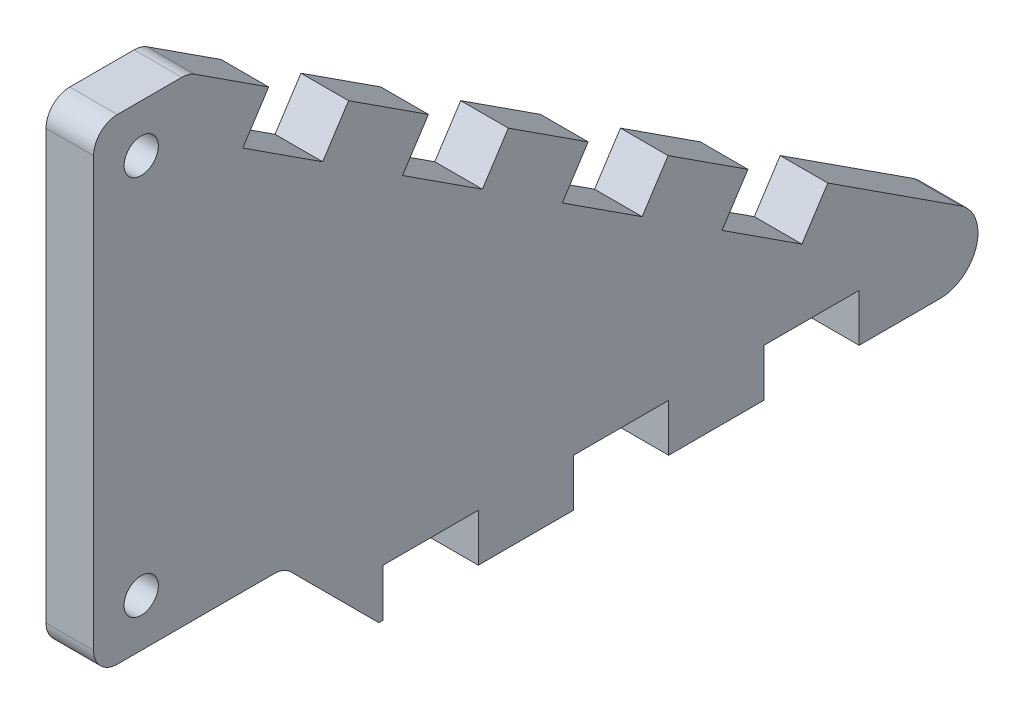
SolidWorks part; units mm, degrees
material "Custom Plastic"
ref_plane "Front Plane" through (0, 0, 0) normal (0, 0, 1) x (1, 0, 0)
ref_plane "Top Plane" through (0, 0, 0) normal (0, 1, 0) x (1, 0, 0)
ref_plane "Right Plane" through (0, 0, 0) normal (1, 0, 0) x (0, 0, -1)
sketch "Sketch2" plane through (0, 0, 0) normal (1, 0, 0) x (0, 0, -1)
  line L0 (0, 0) -> (0, 26.924) construction
  line L1 (0, 26.924) -> (0, 77.724) construction
  line L2 (-65.278, 77.724) -> (0, 77.724) construction
  line L3 (-71.628, 77.724) -> (-71.628, 26.924) construction
  line L4 (-71.628, 26.924) -> (0, 26.924) construction
  line L5 (-45.72, 0) -> (45.72, 0)
  line L6 (-77.978, 84.074) -> (-77.978, 20.574)
  line L7 (45.72, 7.9375) -> (-45.72, 7.9375)
  line L8 (45.72, 0) -> (52.07, 0)
  line L9 (-77.978, 20.574) -> (-45.72, 0)
  line L10 (-65.278, 84.074) -> (52.07, 7.9375)
  line L11 (-71.628, 77.724) -> (-71.628, 84.074) construction
  line L12 (-71.628, 77.724) -> (-77.978, 77.724) construction
  line L13 (-71.628, 26.924) -> (-77.978, 26.924) construction
  line L14 (-71.628, 26.924) -> (-71.628, 20.574) construction
  line L15 (-65.278, 84.074) -> (-77.978, 84.074)
  line L16 (-71.628, 77.724) -> (-65.278, 77.724) construction
  line L17 (-52.578, 20.574) -> (-39.9415, 7.9375)
  line L18 (-65.278, 77.724) -> (-65.278, 84.074) construction
  line L19 (-77.978, 20.574) -> (-52.578, 20.574)
  line L21 (52.07, 0) -> (52.07, 7.9375)
  line L22 (52.07, 7.9375) -> (45.72, 7.9375)
  circle A0 centre (-71.628, 77.724) radius 2.286
  circle A1 centre (-71.628, 26.924) radius 2.286
  point P0 (0, 0)
  point P1 (-71.628, 77.724)
  point P3 (-71.628, 26.924)
  dimension "D4" = 4.572
  dimension "D7" = 6.35
  dimension "D1" = 50.8
  dimension "D2" = 26.924
  dimension "D3" = 71.628
  dimension "D5" = 7.9375
  dimension "D6" = 91.44
  dimension "D8" = 6.35
  dimension "D9" = 25.4
  dimension "D10" = 45
extrude "Main" add sketch "Sketch2" along normal blind 6.35 contours L7 A1 A0 | L7 region at (0, 37.2066, 31.7898)
sketch "Sketch5" plane through (6.35, 0, 0) normal (1, 0, 0) x (0, 0, -1)
  line L0 (-39.37, 7.9375) -> (-39.37, 14.2875)
  line L1 (52.07, 7.9375) -> (-39.9415, 7.9375) construction
  line L2 (-39.37, 14.2875) -> (-26.67, 14.2875)
  line L3 (-26.67, 14.2875) -> (-26.67, 7.9375)
  line L4 (-26.67, 7.9375) -> (-13.97, 7.9375) construction
  line L5 (-13.97, 7.9375) -> (-13.97, 14.2875)
  line L6 (-13.97, 14.2875) -> (-1.27, 14.2875)
  line L7 (-1.27, 14.2875) -> (-1.27, 7.9375)
  line L8 (-1.27, 7.9375) -> (11.43, 7.9375) construction
  line L9 (11.43, 7.9375) -> (11.43, 14.2875)
  line L10 (11.43, 14.2875) -> (24.13, 14.2875)
  line L11 (24.13, 14.2875) -> (24.13, 7.9375)
  line L12 (-65.278, 84.074) -> (-54.624, 77.1616) construction
  line L13 (-39.37, 7.9375) -> (-26.67, 7.9375)
  line L14 (-13.97, 7.9375) -> (-1.27, 7.9375)
  line L15 (11.43, 7.9375) -> (24.13, 7.9375)
  line L16 (19.9542, 28.7745) -> (16.498, 23.4475)
  line L17 (-65.278, 84.074) -> (52.07, 7.9375) construction
  line L18 (16.498, 23.4475) -> (5.844, 30.36)
  line L19 (5.844, 30.36) -> (9.3002, 35.687)
  line L20 (9.3002, 35.687) -> (19.9542, 28.7745)
  line L21 (-15.4641, 44.1848) -> (-12.0079, 49.5118)
  line L22 (-4.8101, 37.2724) -> (-15.4641, 44.1848)
  line L23 (-1.3538, 42.5994) -> (-4.8101, 37.2724)
  line L24 (-12.0079, 49.5118) -> (-1.3538, 42.5994)
  line L25 (-36.7721, 58.0097) -> (-33.3159, 63.3367)
  line L26 (-26.1181, 51.0973) -> (-36.7721, 58.0097)
  line L27 (-22.6619, 56.4243) -> (-26.1181, 51.0973)
  line L28 (-33.3159, 63.3367) -> (-22.6619, 56.4243)
  line L29 (-58.0802, 71.8346) -> (-54.624, 77.1616)
  line L30 (-47.4262, 64.9221) -> (-58.0802, 71.8346)
  line L31 (-43.9699, 70.2491) -> (-47.4262, 64.9221)
  line L32 (-54.624, 77.1616) -> (-43.9699, 70.2491)
  line L33 (-43.9699, 70.2491) -> (-33.3159, 63.3367) construction
  dimension "D1" = 6.35
  dimension "D2" = 12.7
  dimension "D3" = 27.94
  dimension "D4" = 4
extrude "Acrylic Joint" cut sketch "Sketch5" against normal through all
fillet "Fillet4" radius 3.175 4 edges at (3.175, 84.074, 77.978) (3.175, 20.574, 77.978) (3.175, 84.074, 65.278) (3.175, 20.574, 52.578)
fillet "Fillet5" radius 5.08 1 edges at (3.175, 7.9375, -52.07)
